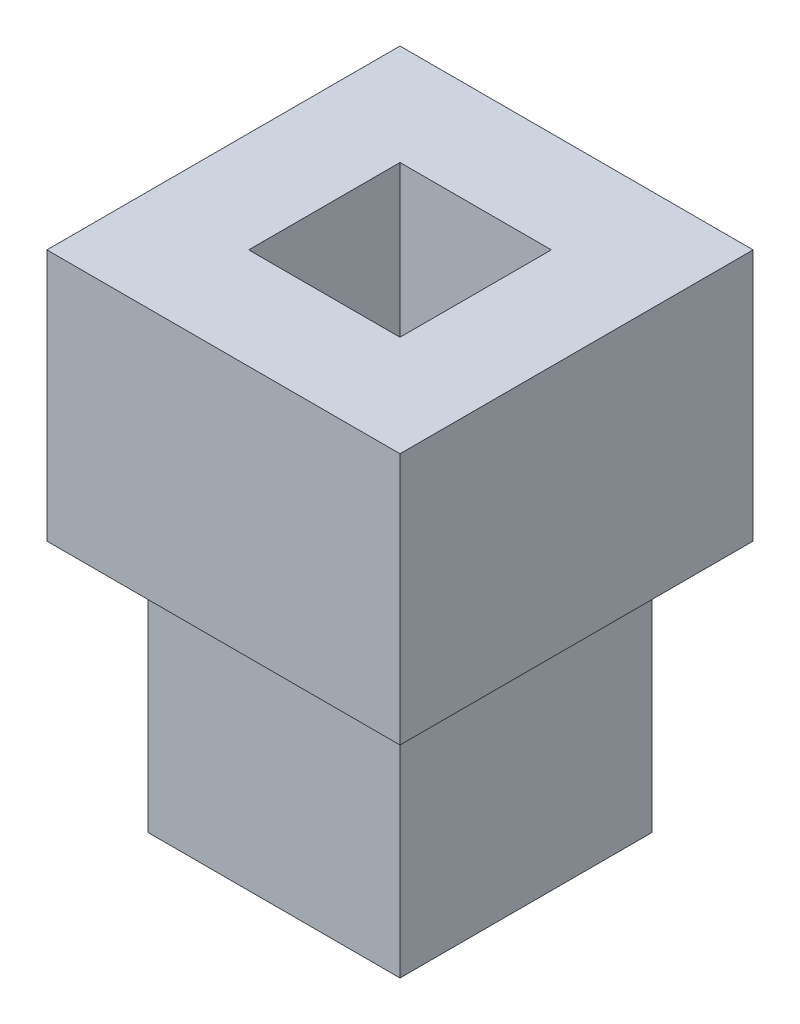
SolidWorks part; units mm, degrees
material "Delrin 2700 NC010, Low Viscosity Acetal Copolymer (SS)"
ref_plane "Front" through (0, 0, 0) normal (0, 0, 1) x (1, 0, 0)
ref_plane "Top" through (0, 0, 0) normal (0, 1, 0) x (1, 0, 0)
ref_plane "Right" through (0, 0, 0) normal (1, 0, 0) x (0, 0, -1)
sketch "Sketch1" plane through (0, 0, 0) normal (0, 1, 0) x (1, 0, 0)
  line L0 (12.5, -12.5) -> (12.5, 12.5)
  line L1 (-17.5, -17.5) -> (17.5, -17.5)
  line L2 (-17.5, -17.5) -> (-17.5, 17.5)
  line L3 (-17.5, 17.5) -> (17.5, 17.5)
  line L4 (17.5, -17.5) -> (17.5, 17.5)
  line L5 (-17.5, -17.5) -> (17.5, 17.5) construction
  line L6 (-17.5, 17.5) -> (17.5, -17.5) construction
  line L7 (-7.5, -7.5) -> (7.5, -7.5)
  line L8 (-7.5, -7.5) -> (-7.5, 7.5)
  line L9 (-7.5, 7.5) -> (7.5, 7.5)
  line L10 (7.5, -7.5) -> (7.5, 7.5)
  line L11 (-7.5, -7.5) -> (7.5, 7.5) construction
  line L12 (-7.5, 7.5) -> (7.5, -7.5) construction
  line L13 (-12.5, 12.5) -> (12.5, 12.5)
  line L14 (-12.5, -12.5) -> (-12.5, 12.5)
  line L15 (-12.5, -12.5) -> (12.5, -12.5)
  point P0 (0, 0)
  point P6 (0, 0)
  dimension "D1" = 35
  dimension "D2" = 10
  dimension "D3" = 5
extrude "Boss-Extrude1" add sketch "Sketch1" along normal blind 25 contours L14 L15 L0 L13 L10 L7 L8 L9 | L1 L4 L3 L2 L15 L14 L13 L0 region at (0, 0, 12.1464) region at (-17.005, 0, 0)
extrude "Boss-Extrude2" add sketch "Sketch1<3>" against normal blind 25 contours L14 L15 L0 L13 L10 L7 L8 L9 region at (0, 0, 12.1464)
sketch "Sketch1<3>" plane through (0, 0, 0) normal (0, 1, 0) x (1, 0, 0) same geometry as "Sketch1"
